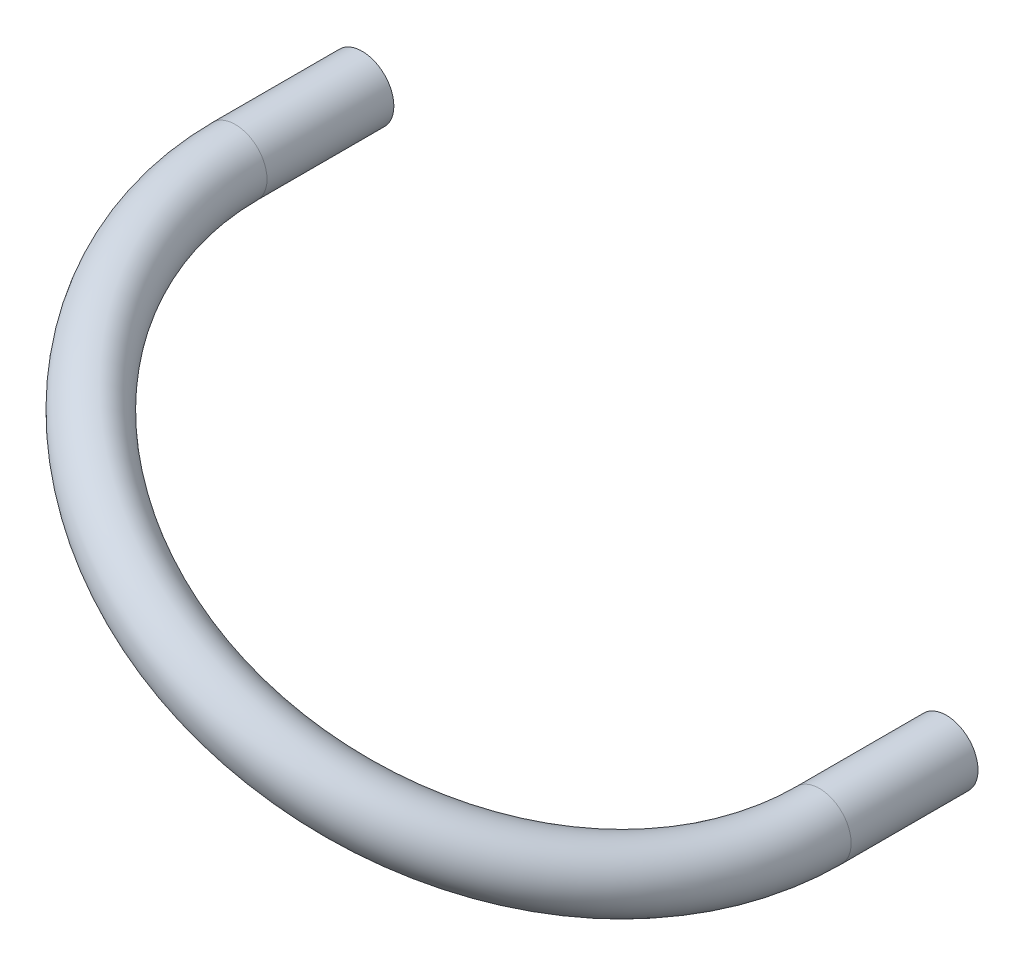
SolidWorks part; units mm, degrees
material "Glass"
ref_plane "Front Plane" through (0, 0, 0) normal (0, 0, 1) x (1, 0, 0)
ref_plane "Top Plane" through (0, 0, 0) normal (0, 1, 0) x (1, 0, 0)
ref_plane "Right Plane" through (0, 0, 0) normal (1, 0, 0) x (0, 0, -1)
sketch3d "3DSketch1"
  line L0 (-133.1073, 76.245, -50.08) -> (-133.1073, 76.245, -69.13)
  line L1 (-133.1073, 76.245, -67.357) -> (-133.1073, 76.245, -72.507) construction
  line L2 (-45.375, 33.75, -50.08) -> (-45.375, 33.75, -69.13)
  arc A0 (-45.375, 33.75, -50.08) -> (-133.1073, 76.245, -50.08) centre (-89.2411, 54.9975, -50.08) ccw
  point P10 (-110.4886, 11.1313, -50.08)
sweep "Sweep-Thin1" add path "3DSketch1" circular profile diameter 9.525 parameters "D1"=2, "D3"=9.525
